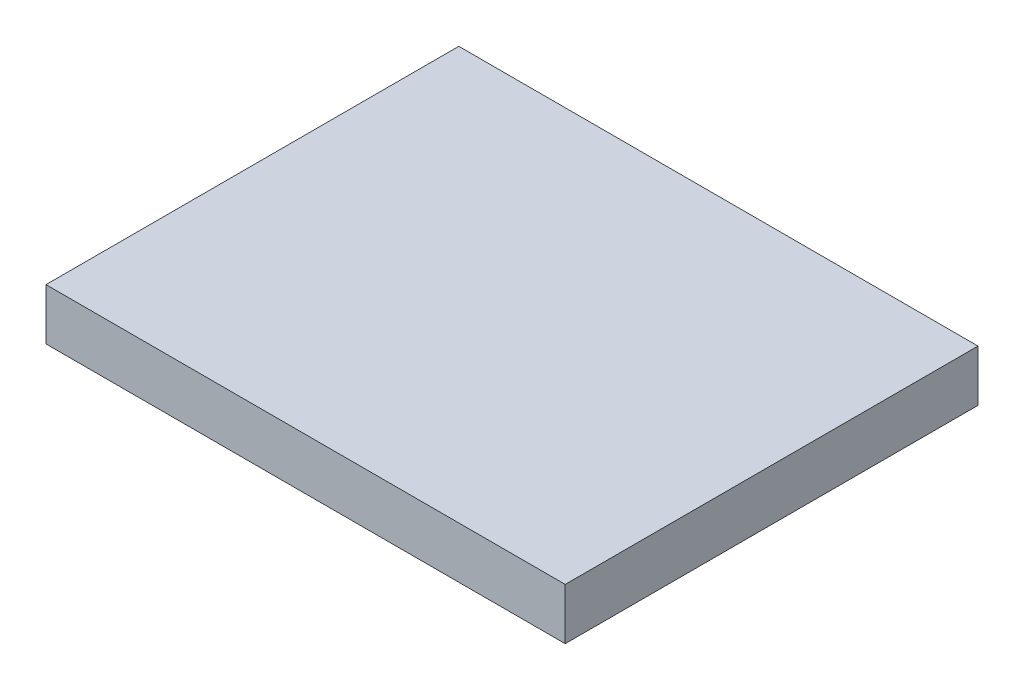
SolidWorks part; units mm, degrees
ref_plane "Front Plane" through (0, 0, 0) normal (0, 0, 1) x (1, 0, 0)
ref_plane "Top Plane" through (0, 0, 0) normal (0, 1, 0) x (1, 0, 0)
ref_plane "Right Plane" through (0, 0, 0) normal (1, 0, 0) x (0, 0, -1)
sketch "Sketch1" plane through (0, 0, 0) normal (0, 1, 0) x (1, 0, 0)
  line L1 (0, 0) -> (283, 0)
  line L2 (0, 0) -> (0, 225)
  line L3 (0, 225) -> (283, 225)
  line L4 (283, 0) -> (283, 225)
  dimension "D1" = 225
  dimension "D2" = 283
extrude "Boss-Extrude1" add sketch "Sketch1" along normal blind 28
sketch "Sketch2" plane through (0, 0, 0) normal (0, -1, 0) x (1, 0, 0)
  line L0 (0, 0) -> (283, 0) construction
  line L1 (283, -225) -> (0, -225) construction
  line L2 (0, -225) -> (0, 0) construction
  line L3 (283, 0) -> (283, -225) construction
  circle A0 centre (25, -42.5) radius 10
  circle A1 centre (25, -200) radius 10
  circle A2 centre (258, -200) radius 10
  circle A3 centre (258, -25) radius 10
  dimension "D1" = 20
  dimension "D10" = 20
  dimension "D11" = 20
  dimension "D12" = 20
  dimension "D2" = 42.5
  dimension "D3" = 25
  dimension "D4" = 25
  dimension "D5" = 25
  dimension "D6" = 25
  dimension "D7" = 25
  dimension "D8" = 25
  dimension "D9" = 25
extrude "Boss-Extrude2" add sketch "Sketch2" along normal blind 6.5
equation "\"Length\"= 283mm"
equation "\"Width\"= 225mm"
equation "\"WallThickness\"= 12.5mm"
equation "\"D1@Sketch1\"=\"Width\""
equation "\"D2@Sketch1\"=\"Length\""
equation "\"UpperWaterJacketThickness\"= 28mm"
equation "\"D1@Boss-Extrude1\"=\"UpperWaterJacketThickness\""
equation "\"UpperWaterJacketPegDiameter\"=20"
equation "\"D1@Sketch2\"=\"UpperWaterJacketPegDiameter\""
equation "\"UpperWaterJacketPegDistance\"=2.5"
equation "\"D2@Sketch2\"=\"WallThickness\"+\"UpperWaterJacketPegDiameter\"/2+\"UpperWaterJacketPegDiameter\""
equation "\"D3@Sketch2\"=\"WallThickness\"+\"UpperWaterJacketPegDiameter\"/2+\"UpperWaterJacketPegDistance\""
equation "\"D4@Sketch2\"=\"WallThickness\"+\"UpperWaterJacketPegDiameter\"/2+\"UpperWaterJacketPegDistance\""
equation "\"D5@Sketch2\"=\"WallThickness\"+\"UpperWaterJacketPegDiameter\"/2+\"UpperWaterJacketPegDistance\""
equation "\"D6@Sketch2\"=\"WallThickness\"+\"UpperWaterJacketPegDiameter\"/2+\"UpperWaterJacketPegDistance\""
equation "\"D7@Sketch2\"=\"WallThickness\"+\"UpperWaterJacketPegDiameter\"/2+\"UpperWaterJacketPegDistance\""
equation "\"D8@Sketch2\"=\"WallThickness\"+\"UpperWaterJacketPegDiameter\"/2+\"UpperWaterJacketPegDistance\""
equation "\"D9@Sketch2\"=\"WallThickness\"+\"UpperWaterJacketPegDiameter\"/2+\"UpperWaterJacketPegDistance\""
equation "\"D10@Sketch2\"=\"UpperWaterJacketPegDiameter\""
equation "\"D11@Sketch2\"=\"UpperWaterJacketPegDiameter\""
equation "\"D12@Sketch2\"=\"UpperWaterJacketPegDiameter\""
equation "\"UpperWaterJacketPegHeight\"=6.5"
equation "\"D1@Boss-Extrude2\"=\"UpperWaterJacketPegHeight\""
equation "\"SpacerHeight\"= 80.2mm"
equation "\"SpacerCornerWidth\"= 10mm"
equation "\"SpacerCornerHeight\"= 60.16mm"
equation "\"SpacerPegDiameter\"= 10mm"
equation "\"SpacerPegHeight\"= 10mm"
equation "\"TubingShort\"= 110mm"
equation "\"TubingLong\"= 175mm"
equation "\"PlateLength\"= 252mm"
equation "\"PlateWidth\"= 190mm"
equation "\"PlateHoleDiameter\"= 5.9mm"
equation "\"PlateHoleBottom\"= 2mm"
equation "\"PlateHoleSide\"= 1.55mm"
equation "\"PlateHoleSpacing\"= 3.1mm"
equation "\"PlateThickness\"= 1.55mm"
equation "\"ReservoirBottom\"= 12.5mm"
equation "\"ReservoirSupportWidth\"= 12mm"
equation "\"ReservoirSupportHeight\"= 15.1mm"
equation "\"ReservoirSupportPlacementHeight\"= 50mm"
equation "\"ReservoirHoleDiameter\"= 12.7mm"
equation "\"ReservoirHoleRight\"= 25mm"
equation "\"ReservoirHoleTop\"= \"ReservoirSupportPlacementHeight\""
equation "\"ReservoirHeight\"= 90mm"
equation "\"ReservoirPortBottom\"= 4mm"
equation "\"ReservoirPortTop\"= 10mm"
equation "\"ReservoirPortWidth\"= 101mm"
equation "\"CustomSpacerWallThickness\" = 6.35mm"
equation "\"CustomSpacerHeight\" = 5in"
equation "\"CustomSpacerRodHoleHeight\" = .75in"
equation "\"CustomSpacerRodHoleDiameter\" = .3125in"
equation "\"ScrewBlockSide\"= .5in"
equation "\"ScrewBlockUpperHeight\" = 16mm"
equation "\"ScrewBlockLowerHeight\" = 16mm"
equation "\"InternalLength\" = \"Length\" - ( 2 * \"WallThickness\" )"
equation "\"InternalWidth\"= \"Width\" - ( 2 * \"WallThickness\" )"
